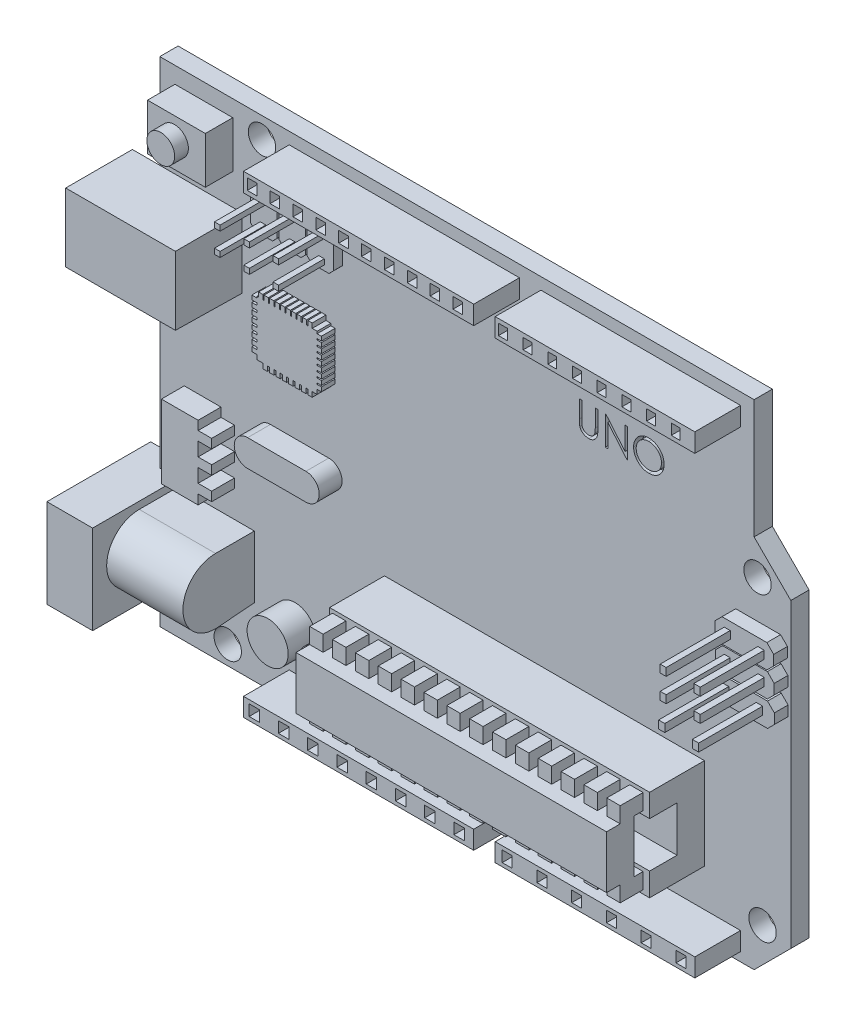
SolidWorks part; units mm, degrees
ref_plane "Front Plane" through (0, 0, 0) normal (0, 0, 1) x (1, 0, 0)
ref_plane "Top Plane" through (0, 0, 0) normal (0, 1, 0) x (1, 0, 0)
ref_plane "Right Plane" through (0, 0, 0) normal (1, 0, 0) x (0, 0, -1)
sketch "Sketch1" plane through (0, 0, 0) normal (0, 0, 1) x (1, 0, 0)
  line L0 (-30.3432, 34.8124) -> (32.6568, 34.8124)
  line L1 (-30.3432, 34.8124) -> (-30.3432, -19.1876)
  line L2 (-30.3432, -19.1876) -> (34.6568, -19.1876)
  line L3 (34.6568, -19.1876) -> (38.6728, -15.1716)
  line L4 (38.6728, -15.1716) -> (38.6728, 17.7963)
  line L5 (38.6728, 17.7963) -> (34.6568, 21.8124)
  line L6 (34.6568, 21.8124) -> (34.6568, 34.8124)
  line L7 (34.6568, 34.8124) -> (32.6568, 34.8124)
  dimension "D1" = 65
  dimension "D2" = 54
  dimension "D3" = 63
  dimension "D4" = 13
extrude "Boss-Extrude1" add sketch "Sketch1" along normal blind 2
sketch "Sketch2" plane through (0, 0, 2) normal (0, 0, 1) x (1, 0, 0)
  line L0 (-16.1908, 33.5246) -> (8.9881, 33.5246)
  line L1 (8.9881, 33.5246) -> (8.9881, 31.4811)
  line L2 (8.9881, 31.4811) -> (-16.1908, 31.4811)
  line L3 (-16.1908, 31.4811) -> (-16.1908, 33.5246)
  line L4 (11.3419, 33.5246) -> (33.1744, 33.5246)
  line L5 (33.1744, 33.5246) -> (33.1744, 31.4811)
  line L6 (33.1744, 31.4811) -> (11.3419, 31.4811)
  line L7 (11.3419, 31.4811) -> (11.3419, 33.5246)
extrude "Boss-Extrude2" add sketch "Sketch2" along normal blind 5
sketch "Sketch3" plane through (0, 0, 7) normal (0, 0, 1) x (1, 0, 0)
  line L0 (8.9881, 33.5246) -> (-16.1908, 33.5246) construction
  line L1 (-15.7782, 33.1261) -> (-14.7285, 33.1261)
  line L2 (-15.7782, 33.1261) -> (-15.7782, 31.9149)
  line L3 (-15.7782, 31.9149) -> (-14.7285, 31.9149)
  line L4 (-14.7285, 33.1261) -> (-14.7285, 31.9149)
  line L5 (-15.7782, 33.1261) -> (-14.7285, 31.9149) construction
  line L6 (-15.7782, 31.9149) -> (-14.7285, 33.1261) construction
  line L7 (-16.1908, 31.4811) -> (8.9881, 31.4811) construction
  line L8 (-13.2782, 33.1261) -> (-12.2285, 33.1261)
  line L9 (-12.2285, 33.1261) -> (-12.2285, 31.9149)
  line L10 (-13.2782, 31.9149) -> (-12.2285, 31.9149)
  line L11 (-13.2782, 33.1261) -> (-13.2782, 31.9149)
  line L12 (-10.7782, 33.1261) -> (-9.7285, 33.1261)
  line L13 (-9.7285, 33.1261) -> (-9.7285, 31.9149)
  line L14 (-10.7782, 31.9149) -> (-9.7285, 31.9149)
  line L15 (-10.7782, 33.1261) -> (-10.7782, 31.9149)
  line L16 (-8.2782, 33.1261) -> (-7.2285, 33.1261)
  line L17 (-7.2285, 33.1261) -> (-7.2285, 31.9149)
  line L18 (-8.2782, 31.9149) -> (-7.2285, 31.9149)
  line L19 (-8.2782, 33.1261) -> (-8.2782, 31.9149)
  line L20 (-5.7782, 33.1261) -> (-4.7285, 33.1261)
  line L21 (-4.7285, 33.1261) -> (-4.7285, 31.9149)
  line L22 (-5.7782, 31.9149) -> (-4.7285, 31.9149)
  line L23 (-5.7782, 33.1261) -> (-5.7782, 31.9149)
  line L24 (-3.2782, 33.1261) -> (-2.2285, 33.1261)
  line L25 (-2.2285, 33.1261) -> (-2.2285, 31.9149)
  line L26 (-3.2782, 31.9149) -> (-2.2285, 31.9149)
  line L27 (-3.2782, 33.1261) -> (-3.2782, 31.9149)
  line L28 (-0.7782, 33.1261) -> (0.2715, 33.1261)
  line L29 (0.2715, 33.1261) -> (0.2715, 31.9149)
  line L30 (-0.7782, 31.9149) -> (0.2715, 31.9149)
  line L31 (-0.7782, 33.1261) -> (-0.7782, 31.9149)
  line L32 (1.7218, 33.1261) -> (2.7715, 33.1261)
  line L33 (2.7715, 33.1261) -> (2.7715, 31.9149)
  line L34 (1.7218, 31.9149) -> (2.7715, 31.9149)
  line L35 (1.7218, 33.1261) -> (1.7218, 31.9149)
  line L36 (4.2218, 33.1261) -> (5.2715, 33.1261)
  line L37 (5.2715, 33.1261) -> (5.2715, 31.9149)
  line L38 (4.2218, 31.9149) -> (5.2715, 31.9149)
  line L39 (4.2218, 33.1261) -> (4.2218, 31.9149)
  line L40 (6.7218, 33.1261) -> (7.7715, 33.1261)
  line L41 (7.7715, 33.1261) -> (7.7715, 31.9149)
  line L42 (6.7218, 31.9149) -> (7.7715, 31.9149)
  line L43 (6.7218, 33.1261) -> (6.7218, 31.9149)
  point P0 (-15.2533, 32.5205)
  dimension "D1" = 0.3985
  dimension "D2" = 0.4337
  dimension "D3" = 10
extrude "Cut-Extrude1" cut sketch "Sketch3" against normal blind 5
sketch "Sketch4" plane through (0, 0, 7) normal (0, 0, 1) x (1, 0, 0)
  line L0 (33.1744, 33.5246) -> (11.3419, 33.5246) construction
  line L1 (11.6967, 33.0774) -> (12.6722, 33.0774)
  line L2 (11.6967, 33.0774) -> (11.6967, 31.8986)
  line L3 (11.6967, 31.8986) -> (12.6722, 31.8986)
  line L4 (12.6722, 33.0774) -> (12.6722, 31.8986)
  line L5 (11.6967, 33.0774) -> (12.6722, 31.8986) construction
  line L6 (11.6967, 31.8986) -> (12.6722, 33.0774) construction
  line L7 (11.3419, 31.4811) -> (33.1744, 31.4811) construction
  line L8 (14.3967, 33.0774) -> (15.3722, 33.0774)
  line L9 (15.3722, 33.0774) -> (15.3722, 31.8986)
  line L10 (14.3967, 31.8986) -> (15.3722, 31.8986)
  line L11 (14.3967, 33.0774) -> (14.3967, 31.8986)
  line L12 (17.0967, 33.0774) -> (18.0722, 33.0774)
  line L13 (18.0722, 33.0774) -> (18.0722, 31.8986)
  line L14 (17.0967, 31.8986) -> (18.0722, 31.8986)
  line L15 (17.0967, 33.0774) -> (17.0967, 31.8986)
  line L16 (19.7967, 33.0774) -> (20.7722, 33.0774)
  line L17 (20.7722, 33.0774) -> (20.7722, 31.8986)
  line L18 (19.7967, 31.8986) -> (20.7722, 31.8986)
  line L19 (19.7967, 33.0774) -> (19.7967, 31.8986)
  line L20 (22.4967, 33.0774) -> (23.4722, 33.0774)
  line L21 (23.4722, 33.0774) -> (23.4722, 31.8986)
  line L22 (22.4967, 31.8986) -> (23.4722, 31.8986)
  line L23 (22.4967, 33.0774) -> (22.4967, 31.8986)
  line L24 (25.1967, 33.0774) -> (26.1722, 33.0774)
  line L25 (26.1722, 33.0774) -> (26.1722, 31.8986)
  line L26 (25.1967, 31.8986) -> (26.1722, 31.8986)
  line L27 (25.1967, 33.0774) -> (25.1967, 31.8986)
  line L28 (27.8967, 33.0774) -> (28.8722, 33.0774)
  line L29 (28.8722, 33.0774) -> (28.8722, 31.8986)
  line L30 (27.8967, 31.8986) -> (28.8722, 31.8986)
  line L31 (27.8967, 33.0774) -> (27.8967, 31.8986)
  line L32 (30.5967, 33.0774) -> (31.5722, 33.0774)
  line L33 (31.5722, 33.0774) -> (31.5722, 31.8986)
  line L34 (30.5967, 31.8986) -> (31.5722, 31.8986)
  line L35 (30.5967, 33.0774) -> (30.5967, 31.8986)
  point P0 (12.1845, 32.488)
  dimension "D1" = 0.4472
  dimension "D2" = 0.4175
  dimension "D3" = 8
extrude "Cut-Extrude2" cut sketch "Sketch4" against normal blind 5
sketch "Sketch5" plane through (0, 0, 2) normal (0, 0, 1) x (1, 0, 0)
  line L0 (-16.1908, -16.2122) -> (8.9881, -16.2122)
  line L1 (8.9881, -16.2122) -> (8.9881, -18.2122)
  line L2 (8.9881, -18.2122) -> (-16.1908, -18.2122)
  line L3 (-16.1908, -18.2122) -> (-16.1908, -16.2122)
  line L4 (-16.1908, 33.5246) -> (-16.1908, 31.4811) construction
  line L5 (8.9881, 31.4811) -> (8.9881, 33.5246) construction
  line L8 (11.3419, -16.2122) -> (33.1744, -16.2122)
  line L9 (33.1744, -16.2122) -> (33.1744, -18.2122)
  line L10 (33.1744, -18.2122) -> (11.3419, -18.2122)
  line L11 (11.3419, -16.2122) -> (11.3419, -18.2122)
  line L12 (11.3419, 33.5246) -> (11.3419, 31.4811) construction
  line L13 (33.1744, 31.4811) -> (33.1744, 33.5246) construction
extrude "Boss-Extrude3" add sketch "Sketch5" along normal blind 5
sketch "Sketch6" plane through (0, 0, 7) normal (0, 0, 1) x (1, 0, 0)
  line L0 (8.9881, -16.2122) -> (-16.1908, -16.2122) construction
  line L1 (-15.572, -16.6122) -> (-14.4338, -16.6122)
  line L2 (-15.572, -16.6122) -> (-15.572, -17.8122)
  line L3 (-15.572, -17.8122) -> (-14.4338, -17.8122)
  line L4 (-14.4338, -16.6122) -> (-14.4338, -17.8122)
  line L5 (-15.572, -16.6122) -> (-14.4338, -17.8122) construction
  line L6 (-15.572, -17.8122) -> (-14.4338, -16.6122) construction
  line L7 (-16.1908, -18.2122) -> (8.9881, -18.2122) construction
  line L8 (-12.372, -16.6122) -> (-11.2338, -16.6122)
  line L9 (-11.2338, -16.6122) -> (-11.2338, -17.8122)
  line L10 (-12.372, -17.8122) -> (-11.2338, -17.8122)
  line L11 (-12.372, -16.6122) -> (-12.372, -17.8122)
  line L12 (-9.172, -16.6122) -> (-8.0338, -16.6122)
  line L13 (-8.0338, -16.6122) -> (-8.0338, -17.8122)
  line L14 (-9.172, -17.8122) -> (-8.0338, -17.8122)
  line L15 (-9.172, -16.6122) -> (-9.172, -17.8122)
  line L16 (-5.972, -16.6122) -> (-4.8338, -16.6122)
  line L17 (-4.8338, -16.6122) -> (-4.8338, -17.8122)
  line L18 (-5.972, -17.8122) -> (-4.8338, -17.8122)
  line L19 (-5.972, -16.6122) -> (-5.972, -17.8122)
  line L20 (-2.772, -16.6122) -> (-1.6338, -16.6122)
  line L21 (-1.6338, -16.6122) -> (-1.6338, -17.8122)
  line L22 (-2.772, -17.8122) -> (-1.6338, -17.8122)
  line L23 (-2.772, -16.6122) -> (-2.772, -17.8122)
  line L24 (0.428, -16.6122) -> (1.5662, -16.6122)
  line L25 (1.5662, -16.6122) -> (1.5662, -17.8122)
  line L26 (0.428, -17.8122) -> (1.5662, -17.8122)
  line L27 (0.428, -16.6122) -> (0.428, -17.8122)
  line L28 (3.628, -16.6122) -> (4.7662, -16.6122)
  line L29 (4.7662, -16.6122) -> (4.7662, -17.8122)
  line L30 (3.628, -17.8122) -> (4.7662, -17.8122)
  line L31 (3.628, -16.6122) -> (3.628, -17.8122)
  line L32 (6.828, -16.6122) -> (7.9662, -16.6122)
  line L33 (7.9662, -16.6122) -> (7.9662, -17.8122)
  line L34 (6.828, -17.8122) -> (7.9662, -17.8122)
  line L35 (6.828, -16.6122) -> (6.828, -17.8122)
  point P0 (-15.0029, -17.2122)
  dimension "D1" = 0.4
  dimension "D2" = 0.4
  dimension "D3" = 8
extrude "Cut-Extrude3" cut sketch "Sketch6" against normal blind 5
sketch "Sketch7" plane through (0, 0, 7) normal (0, 0, 1) x (1, 0, 0)
  line L0 (33.1744, -16.2122) -> (11.3419, -16.2122) construction
  line L1 (12.1099, -16.6122) -> (13.1873, -16.6122)
  line L2 (12.1099, -16.6122) -> (12.1099, -17.8122)
  line L3 (12.1099, -17.8122) -> (13.1873, -17.8122)
  line L4 (13.1873, -16.6122) -> (13.1873, -17.8122)
  line L5 (12.1099, -16.6122) -> (13.1873, -17.8122) construction
  line L6 (12.1099, -17.8122) -> (13.1873, -16.6122) construction
  line L7 (11.3419, -18.2122) -> (33.1744, -18.2122) construction
  line L8 (15.9099, -16.6122) -> (16.9873, -16.6122)
  line L9 (16.9873, -16.6122) -> (16.9873, -17.8122)
  line L10 (15.9099, -17.8122) -> (16.9873, -17.8122)
  line L11 (15.9099, -16.6122) -> (15.9099, -17.8122)
  line L12 (19.7099, -16.6122) -> (20.7873, -16.6122)
  line L13 (20.7873, -16.6122) -> (20.7873, -17.8122)
  line L14 (19.7099, -17.8122) -> (20.7873, -17.8122)
  line L15 (19.7099, -16.6122) -> (19.7099, -17.8122)
  line L16 (23.5099, -16.6122) -> (24.5873, -16.6122)
  line L17 (24.5873, -16.6122) -> (24.5873, -17.8122)
  line L18 (23.5099, -17.8122) -> (24.5873, -17.8122)
  line L19 (23.5099, -16.6122) -> (23.5099, -17.8122)
  line L20 (27.3099, -16.6122) -> (28.3873, -16.6122)
  line L21 (28.3873, -16.6122) -> (28.3873, -17.8122)
  line L22 (27.3099, -17.8122) -> (28.3873, -17.8122)
  line L23 (27.3099, -16.6122) -> (27.3099, -17.8122)
  line L24 (31.1099, -16.6122) -> (32.1873, -16.6122)
  line L25 (32.1873, -16.6122) -> (32.1873, -17.8122)
  line L26 (31.1099, -17.8122) -> (32.1873, -17.8122)
  line L27 (31.1099, -16.6122) -> (31.1099, -17.8122)
  point P0 (12.6486, -17.2122)
  dimension "D1" = 0.4
  dimension "D2" = 0.4
  dimension "D3" = 6
extrude "Cut-Extrude4" cut sketch "Sketch7" against normal blind 5
sketch "Sketch8" plane through (0, 0, 2) normal (0, 0, 1) x (1, 0, 0)
  circle A0 centre (35.0332, 18.1728) radius 1.5
  circle A1 centre (35.582, -14.5072) radius 1.5
  circle A2 centre (-22.9132, -17.1286) radius 1.5
  circle A3 centre (-19.1683, 32.5286) radius 1.5
  dimension "D1" = 3
  dimension "D2" = 3
  dimension "D3" = 3
  dimension "D4" = 3
extrude "Cut-Extrude5" cut sketch "Sketch8" against normal blind 5
sketch "Sketch9" plane through (0, 0, 2) normal (0, 0, 1) x (1, 0, 0)
  line L1 (-5.7706, -2.0923) -> (29.2294, -2.0923)
  line L2 (-5.7706, -2.0923) -> (-5.7706, -12.0923)
  line L3 (-5.7706, -12.0923) -> (29.2294, -12.0923)
  line L4 (29.2294, -2.0923) -> (29.2294, -12.0923)
  line L5 (-5.7706, -2.0923) -> (29.2294, -12.0923) construction
  line L6 (-5.7706, -12.0923) -> (29.2294, -2.0923) construction
  point P0 (11.7294, -7.0923)
  dimension "D1" = 35
  dimension "D2" = 10
extrude "Boss-Extrude4" add sketch "Sketch9" along normal blind 6
sketch "Sketch10" plane through (29.2294, 0, 0) normal (1, 0, 0) x (0, 0, -1)
  line L0 (-8, -4.5923) -> (-5.0036, -4.5923)
  line L1 (-8, -12.0923) -> (-8, -2.0923) construction
  line L2 (-5.0036, -4.5923) -> (-5.0036, -9.5561)
  line L3 (-5.0036, -9.5561) -> (-8, -9.5561)
  line L4 (-8, -2.0923) -> (-2, -2.0923) construction
  line L5 (-8, -12.0923) -> (-2, -12.0923) construction
  line L6 (-8, -4.5923) -> (-8, -9.5561)
  dimension "D1" = 2.5
  dimension "D2" = 2.5362
extrude "Cut-Extrude7" cut sketch "Sketch10" against normal blind 35
sketch "Sketch11" plane through (0, 0, 8) normal (0, 0, 1) x (1, 0, 0)
  line L0 (29.2294, -2.0923) -> (-5.7706, -2.0923) construction
  line L1 (-5.4532, -2.4705) -> (-3.984, -2.4705)
  line L2 (-5.4532, -2.4705) -> (-5.4532, -4.1923)
  line L3 (-5.4532, -4.1923) -> (-3.984, -4.1923)
  line L4 (-3.984, -2.4705) -> (-3.984, -4.1923)
  line L5 (-5.4532, -2.4705) -> (-3.984, -4.1923) construction
  line L6 (-5.4532, -4.1923) -> (-3.984, -2.4705) construction
  line L7 (-5.7706, -4.5923) -> (29.2294, -4.5923) construction
  line L8 (-5.4532, -9.9563) -> (-3.984, -11.6781) construction
  line L9 (-5.4532, -9.9563) -> (-5.4532, -11.6781)
  line L10 (-5.4532, -11.6781) -> (-3.984, -11.6781)
  line L11 (-3.984, -9.9563) -> (-3.984, -11.6781)
  line L12 (-5.4532, -11.6781) -> (-3.984, -9.9563) construction
  line L13 (-5.4532, -9.9563) -> (-3.984, -9.9563)
  line L14 (-2.9532, -2.4705) -> (-1.484, -2.4705)
  line L15 (-1.484, -2.4705) -> (-1.484, -4.1923)
  line L16 (-2.9532, -4.1923) -> (-1.484, -4.1923)
  line L17 (-2.9532, -2.4705) -> (-2.9532, -4.1923)
  line L18 (-2.9532, -9.9563) -> (-1.484, -9.9563)
  line L19 (-1.484, -9.9563) -> (-1.484, -11.6781)
  line L20 (-2.9532, -11.6781) -> (-1.484, -11.6781)
  line L21 (-2.9532, -9.9563) -> (-2.9532, -11.6781)
  line L22 (-0.4532, -2.4705) -> (1.016, -2.4705)
  line L23 (1.016, -2.4705) -> (1.016, -4.1923)
  line L24 (-0.4532, -4.1923) -> (1.016, -4.1923)
  line L25 (-0.4532, -2.4705) -> (-0.4532, -4.1923)
  line L26 (-0.4532, -9.9563) -> (1.016, -9.9563)
  line L27 (1.016, -9.9563) -> (1.016, -11.6781)
  line L28 (-0.4532, -11.6781) -> (1.016, -11.6781)
  line L29 (-0.4532, -9.9563) -> (-0.4532, -11.6781)
  line L30 (2.0468, -2.4705) -> (3.516, -2.4705)
  line L31 (3.516, -2.4705) -> (3.516, -4.1923)
  line L32 (2.0468, -4.1923) -> (3.516, -4.1923)
  line L33 (2.0468, -2.4705) -> (2.0468, -4.1923)
  line L34 (2.0468, -9.9563) -> (3.516, -9.9563)
  line L35 (3.516, -9.9563) -> (3.516, -11.6781)
  line L36 (2.0468, -11.6781) -> (3.516, -11.6781)
  line L37 (2.0468, -9.9563) -> (2.0468, -11.6781)
  line L38 (4.5468, -2.4705) -> (6.016, -2.4705)
  line L39 (6.016, -2.4705) -> (6.016, -4.1923)
  line L40 (4.5468, -4.1923) -> (6.016, -4.1923)
  line L41 (4.5468, -2.4705) -> (4.5468, -4.1923)
  line L42 (4.5468, -9.9563) -> (6.016, -9.9563)
  line L43 (6.016, -9.9563) -> (6.016, -11.6781)
  line L44 (4.5468, -11.6781) -> (6.016, -11.6781)
  line L45 (4.5468, -9.9563) -> (4.5468, -11.6781)
  line L46 (7.0468, -2.4705) -> (8.516, -2.4705)
  line L47 (8.516, -2.4705) -> (8.516, -4.1923)
  line L48 (7.0468, -4.1923) -> (8.516, -4.1923)
  line L49 (7.0468, -2.4705) -> (7.0468, -4.1923)
  line L50 (7.0468, -9.9563) -> (8.516, -9.9563)
  line L51 (8.516, -9.9563) -> (8.516, -11.6781)
  line L52 (7.0468, -11.6781) -> (8.516, -11.6781)
  line L53 (7.0468, -9.9563) -> (7.0468, -11.6781)
  line L54 (9.5468, -2.4705) -> (11.016, -2.4705)
  line L55 (11.016, -2.4705) -> (11.016, -4.1923)
  line L56 (9.5468, -4.1923) -> (11.016, -4.1923)
  line L57 (9.5468, -2.4705) -> (9.5468, -4.1923)
  line L58 (9.5468, -9.9563) -> (11.016, -9.9563)
  line L59 (11.016, -9.9563) -> (11.016, -11.6781)
  line L60 (9.5468, -11.6781) -> (11.016, -11.6781)
  line L61 (9.5468, -9.9563) -> (9.5468, -11.6781)
  line L62 (12.0468, -2.4705) -> (13.516, -2.4705)
  line L63 (13.516, -2.4705) -> (13.516, -4.1923)
  line L64 (12.0468, -4.1923) -> (13.516, -4.1923)
  line L65 (12.0468, -2.4705) -> (12.0468, -4.1923)
  line L66 (12.0468, -9.9563) -> (13.516, -9.9563)
  line L67 (13.516, -9.9563) -> (13.516, -11.6781)
  line L68 (12.0468, -11.6781) -> (13.516, -11.6781)
  line L69 (12.0468, -9.9563) -> (12.0468, -11.6781)
  line L70 (14.5468, -2.4705) -> (16.016, -2.4705)
  line L71 (16.016, -2.4705) -> (16.016, -4.1923)
  line L72 (14.5468, -4.1923) -> (16.016, -4.1923)
  line L73 (14.5468, -2.4705) -> (14.5468, -4.1923)
  line L74 (14.5468, -9.9563) -> (16.016, -9.9563)
  line L75 (16.016, -9.9563) -> (16.016, -11.6781)
  line L76 (14.5468, -11.6781) -> (16.016, -11.6781)
  line L77 (14.5468, -9.9563) -> (14.5468, -11.6781)
  line L78 (17.0468, -2.4705) -> (18.516, -2.4705)
  line L79 (18.516, -2.4705) -> (18.516, -4.1923)
  line L80 (17.0468, -4.1923) -> (18.516, -4.1923)
  line L81 (17.0468, -2.4705) -> (17.0468, -4.1923)
  line L82 (17.0468, -9.9563) -> (18.516, -9.9563)
  line L83 (18.516, -9.9563) -> (18.516, -11.6781)
  line L84 (17.0468, -11.6781) -> (18.516, -11.6781)
  line L85 (17.0468, -9.9563) -> (17.0468, -11.6781)
  line L86 (19.5468, -2.4705) -> (21.016, -2.4705)
  line L87 (21.016, -2.4705) -> (21.016, -4.1923)
  line L88 (19.5468, -4.1923) -> (21.016, -4.1923)
  line L89 (19.5468, -2.4705) -> (19.5468, -4.1923)
  line L90 (19.5468, -9.9563) -> (21.016, -9.9563)
  line L91 (21.016, -9.9563) -> (21.016, -11.6781)
  line L92 (19.5468, -11.6781) -> (21.016, -11.6781)
  line L93 (19.5468, -9.9563) -> (19.5468, -11.6781)
  line L94 (22.0468, -2.4705) -> (23.516, -2.4705)
  line L95 (23.516, -2.4705) -> (23.516, -4.1923)
  line L96 (22.0468, -4.1923) -> (23.516, -4.1923)
  line L97 (22.0468, -2.4705) -> (22.0468, -4.1923)
  line L98 (22.0468, -9.9563) -> (23.516, -9.9563)
  line L99 (23.516, -9.9563) -> (23.516, -11.6781)
  line L100 (22.0468, -11.6781) -> (23.516, -11.6781)
  line L101 (22.0468, -9.9563) -> (22.0468, -11.6781)
  line L102 (24.5468, -2.4705) -> (26.016, -2.4705)
  line L103 (26.016, -2.4705) -> (26.016, -4.1923)
  line L104 (24.5468, -4.1923) -> (26.016, -4.1923)
  line L105 (24.5468, -2.4705) -> (24.5468, -4.1923)
  line L106 (24.5468, -9.9563) -> (26.016, -9.9563)
  line L107 (26.016, -9.9563) -> (26.016, -11.6781)
  line L108 (24.5468, -11.6781) -> (26.016, -11.6781)
  line L109 (24.5468, -9.9563) -> (24.5468, -11.6781)
  line L110 (27.0468, -2.4705) -> (28.516, -2.4705)
  line L111 (28.516, -2.4705) -> (28.516, -4.1923)
  line L112 (27.0468, -4.1923) -> (28.516, -4.1923)
  line L113 (27.0468, -2.4705) -> (27.0468, -4.1923)
  line L114 (27.0468, -9.9563) -> (28.516, -9.9563)
  line L115 (28.516, -9.9563) -> (28.516, -11.6781)
  line L116 (27.0468, -11.6781) -> (28.516, -11.6781)
  line L117 (27.0468, -9.9563) -> (27.0468, -11.6781)
  point P0 (-4.7186, -3.3314)
  point P9 (-4.7186, -10.8172)
  dimension "D1" = 0.3782
  dimension "D2" = 0.4
  dimension "D3" = 14
extrude "Cut-Extrude8" cut sketch "Sketch11" against normal blind 5
sketch "Sketch12" plane through (0, 0, 8) normal (0, 0, 1) x (1, 0, 0)
  line L0 (-5.4532, -2.4705) -> (-3.984, -2.4705)
  line L1 (-3.984, -2.4705) -> (-3.984, -4.1923)
  line L2 (-3.984, -4.1923) -> (-5.4532, -4.1923)
  line L3 (-5.4532, -4.1923) -> (-5.4532, -2.4705)
  line L4 (-5.4532, -9.9563) -> (-5.4532, -11.6781)
  line L5 (-5.4532, -11.6781) -> (-3.984, -11.6781)
  line L6 (-3.984, -11.6781) -> (-3.984, -9.9563)
  line L7 (-3.984, -9.9563) -> (-5.4532, -9.9563)
  line L8 (-2.9532, -2.4705) -> (-1.484, -2.4705)
  line L9 (-1.484, -2.4705) -> (-1.484, -4.1923)
  line L10 (-1.484, -4.1923) -> (-2.9532, -4.1923)
  line L11 (-2.9532, -4.1923) -> (-2.9532, -2.4705)
  line L12 (-1.484, -9.9563) -> (-2.9532, -9.9563)
  line L13 (-1.484, -11.6781) -> (-1.484, -9.9563)
  line L14 (-2.9532, -11.6781) -> (-1.484, -11.6781)
  line L15 (-2.9532, -9.9563) -> (-2.9532, -11.6781)
  line L16 (-0.4532, -2.4705) -> (1.016, -2.4705)
  line L17 (1.016, -2.4705) -> (1.016, -4.1923)
  line L18 (1.016, -4.1923) -> (-0.4532, -4.1923)
  line L19 (-0.4532, -4.1923) -> (-0.4532, -2.4705)
  line L20 (1.016, -9.9563) -> (-0.4532, -9.9563)
  line L21 (1.016, -11.6781) -> (1.016, -9.9563)
  line L22 (-0.4532, -11.6781) -> (1.016, -11.6781)
  line L23 (-0.4532, -9.9563) -> (-0.4532, -11.6781)
  line L24 (2.0468, -2.4705) -> (3.516, -2.4705)
  line L25 (3.516, -2.4705) -> (3.516, -4.1923)
  line L26 (3.516, -4.1923) -> (2.0468, -4.1923)
  line L27 (2.0468, -4.1923) -> (2.0468, -2.4705)
  line L28 (3.516, -9.9563) -> (2.0468, -9.9563)
  line L29 (3.516, -11.6781) -> (3.516, -9.9563)
  line L30 (2.0468, -11.6781) -> (3.516, -11.6781)
  line L31 (2.0468, -9.9563) -> (2.0468, -11.6781)
  line L32 (4.5468, -2.4705) -> (6.016, -2.4705)
  line L33 (6.016, -2.4705) -> (6.016, -4.1923)
  line L34 (6.016, -4.1923) -> (4.5468, -4.1923)
  line L35 (4.5468, -4.1923) -> (4.5468, -2.4705)
  line L36 (6.016, -9.9563) -> (4.5468, -9.9563)
  line L37 (6.016, -11.6781) -> (6.016, -9.9563)
  line L38 (4.5468, -11.6781) -> (6.016, -11.6781)
  line L39 (4.5468, -9.9563) -> (4.5468, -11.6781)
  line L40 (7.0468, -2.4705) -> (8.516, -2.4705)
  line L41 (8.516, -2.4705) -> (8.516, -4.1923)
  line L42 (8.516, -4.1923) -> (7.0468, -4.1923)
  line L43 (7.0468, -4.1923) -> (7.0468, -2.4705)
  line L44 (8.516, -9.9563) -> (7.0468, -9.9563)
  line L45 (8.516, -11.6781) -> (8.516, -9.9563)
  line L46 (7.0468, -11.6781) -> (8.516, -11.6781)
  line L47 (7.0468, -9.9563) -> (7.0468, -11.6781)
  line L48 (9.5468, -2.4705) -> (11.016, -2.4705)
  line L49 (11.016, -2.4705) -> (11.016, -4.1923)
  line L50 (11.016, -4.1923) -> (9.5468, -4.1923)
  line L51 (9.5468, -4.1923) -> (9.5468, -2.4705)
  line L52 (11.016, -9.9563) -> (9.5468, -9.9563)
  line L53 (11.016, -11.6781) -> (11.016, -9.9563)
  line L54 (9.5468, -11.6781) -> (11.016, -11.6781)
  line L55 (9.5468, -9.9563) -> (9.5468, -11.6781)
  line L56 (12.0468, -2.4705) -> (13.516, -2.4705)
  line L57 (13.516, -2.4705) -> (13.516, -4.1923)
  line L58 (13.516, -4.1923) -> (12.0468, -4.1923)
  line L59 (12.0468, -4.1923) -> (12.0468, -2.4705)
  line L60 (13.516, -9.9563) -> (12.0468, -9.9563)
  line L61 (13.516, -11.6781) -> (13.516, -9.9563)
  line L62 (12.0468, -11.6781) -> (13.516, -11.6781)
  line L63 (12.0468, -9.9563) -> (12.0468, -11.6781)
  line L64 (14.5468, -2.4705) -> (16.016, -2.4705)
  line L65 (16.016, -2.4705) -> (16.016, -4.1923)
  line L66 (16.016, -4.1923) -> (14.5468, -4.1923)
  line L67 (14.5468, -4.1923) -> (14.5468, -2.4705)
  line L68 (16.016, -9.9563) -> (14.5468, -9.9563)
  line L69 (16.016, -11.6781) -> (16.016, -9.9563)
  line L70 (14.5468, -11.6781) -> (16.016, -11.6781)
  line L71 (14.5468, -9.9563) -> (14.5468, -11.6781)
  line L72 (17.0468, -2.4705) -> (18.516, -2.4705)
  line L73 (18.516, -2.4705) -> (18.516, -4.1923)
  line L74 (18.516, -4.1923) -> (17.0468, -4.1923)
  line L75 (17.0468, -4.1923) -> (17.0468, -2.4705)
  line L76 (18.516, -9.9563) -> (17.0468, -9.9563)
  line L77 (18.516, -11.6781) -> (18.516, -9.9563)
  line L78 (17.0468, -11.6781) -> (18.516, -11.6781)
  line L79 (17.0468, -9.9563) -> (17.0468, -11.6781)
  line L80 (19.5468, -2.4705) -> (21.016, -2.4705)
  line L81 (21.016, -2.4705) -> (21.016, -4.1923)
  line L82 (21.016, -4.1923) -> (19.5468, -4.1923)
  line L83 (19.5468, -4.1923) -> (19.5468, -2.4705)
  line L84 (21.016, -9.9563) -> (19.5468, -9.9563)
  line L85 (21.016, -11.6781) -> (21.016, -9.9563)
  line L86 (19.5468, -11.6781) -> (21.016, -11.6781)
  line L87 (19.5468, -9.9563) -> (19.5468, -11.6781)
  line L88 (22.0468, -2.4705) -> (23.516, -2.4705)
  line L89 (23.516, -2.4705) -> (23.516, -4.1923)
  line L90 (23.516, -4.1923) -> (22.0468, -4.1923)
  line L91 (22.0468, -4.1923) -> (22.0468, -2.4705)
  line L92 (23.516, -9.9563) -> (22.0468, -9.9563)
  line L93 (23.516, -11.6781) -> (23.516, -9.9563)
  line L94 (22.0468, -11.6781) -> (23.516, -11.6781)
  line L95 (22.0468, -9.9563) -> (22.0468, -11.6781)
  line L96 (24.5468, -2.4705) -> (26.016, -2.4705)
  line L97 (26.016, -2.4705) -> (26.016, -4.1923)
  line L98 (26.016, -4.1923) -> (24.5468, -4.1923)
  line L99 (24.5468, -4.1923) -> (24.5468, -2.4705)
  line L100 (26.016, -9.9563) -> (24.5468, -9.9563)
  line L101 (26.016, -11.6781) -> (26.016, -9.9563)
  line L102 (24.5468, -11.6781) -> (26.016, -11.6781)
  line L103 (24.5468, -9.9563) -> (24.5468, -11.6781)
  line L104 (27.0468, -2.4705) -> (28.516, -2.4705)
  line L105 (28.516, -2.4705) -> (28.516, -4.1923)
  line L106 (28.516, -4.1923) -> (27.0468, -4.1923)
  line L107 (27.0468, -4.1923) -> (27.0468, -2.4705)
  line L108 (28.516, -9.9563) -> (27.0468, -9.9563)
  line L109 (28.516, -11.6781) -> (28.516, -9.9563)
  line L110 (27.0468, -11.6781) -> (28.516, -11.6781)
  line L111 (27.0468, -9.9563) -> (27.0468, -11.6781)
  dimension "D1" = 14
extrude "Boss-Extrude5" add sketch "Sketch12" along normal blind 2.5 and the other way blind 4
sketch "Sketch14" plane through (0, 0, 10.5) normal (0, 0, 1) x (1, 0, 0)
  line L0 (-5.4532, -4.1923) -> (-5.4532, -9.9563)
  line L1 (-5.4532, -9.9563) -> (28.516, -9.9563)
  line L2 (28.516, -9.9563) -> (28.516, -4.1923)
  line L3 (28.516, -4.1923) -> (-5.4532, -4.1923)
extrude "Boss-Extrude6" add sketch "Sketch14" along normal blind 1.5 and the other way blind 1.5
sketch "Sketch15" plane through (0, 0, 2) normal (0, 0, 1) x (1, 0, 0)
  line L0 (32.6488, 14.0019) -> (37.5544, 14.0019)
  line L1 (37.5544, 14.0019) -> (38.3009, 13.2554)
  line L2 (38.3009, 13.2554) -> (38.3009, 12.1534)
  line L3 (38.3009, 12.1534) -> (37.5544, 11.4069)
  line L4 (37.5544, 11.4069) -> (32.6488, 11.4069)
  line L5 (32.6488, 11.4069) -> (31.9023, 12.1534)
  line L6 (31.9023, 12.1534) -> (31.9023, 13.2554)
  line L7 (31.9023, 13.2554) -> (32.6488, 14.0019)
  line L8 (31.9575, 9.4322) -> (31.9575, 10.5342)
  line L9 (38.356, 9.4322) -> (37.6095, 8.6857)
  line L10 (37.6095, 8.6857) -> (32.704, 8.6857)
  line L11 (32.704, 11.2807) -> (37.6095, 11.2807)
  line L12 (31.9575, 10.5342) -> (32.704, 11.2807)
  line L13 (38.356, 10.5342) -> (38.356, 9.4322)
  line L14 (32.704, 8.6857) -> (31.9575, 9.4322)
  line L15 (37.6095, 11.2807) -> (38.356, 10.5342)
  line L16 (37.628, 8.4949) -> (38.3745, 7.7484)
  line L17 (32.7224, 5.9) -> (31.9759, 6.6465)
  line L18 (32.7224, 8.4949) -> (37.628, 8.4949)
  line L19 (38.3745, 7.7484) -> (38.3745, 6.6465)
  line L20 (37.628, 5.9) -> (32.7224, 5.9)
  line L21 (31.9759, 6.6465) -> (31.9759, 7.7484)
  line L22 (38.3745, 6.6465) -> (37.628, 5.9)
  line L23 (31.9759, 7.7484) -> (32.7224, 8.4949)
extrude "Boss-Extrude7" add sketch "Sketch15" along normal blind 1.5
sketch "Sketch16" plane through (0, 0, 3.5) normal (0, 0, 1) x (1, 0, 0)
  line L0 (37.2554, 10.5645) -> (37.2554, 9.7045)
  line L1 (32.8824, 13.1319) -> (33.5564, 13.1319)
  line L2 (32.8824, 13.1319) -> (32.8824, 12.2719)
  line L3 (32.8824, 12.2719) -> (33.5564, 12.2719)
  line L4 (33.5564, 13.1319) -> (33.5564, 12.2719)
  line L5 (32.8824, 13.1319) -> (33.5564, 12.2719) construction
  line L6 (32.8824, 12.2719) -> (33.5564, 13.1319) construction
  line L7 (36.5663, 13.1319) -> (37.2635, 13.1319)
  line L8 (36.5663, 13.1319) -> (36.5663, 12.2719)
  line L9 (36.5663, 12.2719) -> (37.2635, 12.2719)
  line L10 (37.2635, 13.1319) -> (37.2635, 12.2719)
  line L11 (36.5663, 13.1319) -> (37.2635, 12.2719) construction
  line L12 (36.5663, 12.2719) -> (37.2635, 13.1319) construction
  line L13 (36.5581, 9.7045) -> (37.2554, 10.5645) construction
  line L14 (32.8742, 9.7045) -> (33.5483, 9.7045)
  line L15 (32.8742, 10.5645) -> (32.8742, 9.7045)
  line L16 (32.8742, 10.5645) -> (33.5483, 9.7045) construction
  line L17 (36.5581, 10.5645) -> (37.2554, 9.7045) construction
  line L18 (36.5581, 9.7045) -> (37.2554, 9.7045)
  line L19 (32.8742, 9.7045) -> (33.5483, 10.5645) construction
  line L20 (36.5581, 10.5645) -> (37.2554, 10.5645)
  line L21 (36.5581, 10.5645) -> (36.5581, 9.7045)
  line L22 (32.8742, 10.5645) -> (33.5483, 10.5645)
  line L23 (33.5483, 10.5645) -> (33.5483, 9.7045)
  line L24 (36.3976, 6.8925) -> (37.0949, 6.8925)
  line L25 (32.7137, 6.8925) -> (33.3877, 6.8925)
  line L26 (36.3976, 7.7525) -> (36.3976, 6.8925)
  line L27 (36.3976, 7.7525) -> (37.0949, 6.8925) construction
  line L28 (32.7137, 6.8925) -> (33.3877, 7.7525) construction
  line L29 (32.7137, 7.7525) -> (32.7137, 6.8925)
  line L30 (33.3877, 7.7525) -> (33.3877, 6.8925)
  line L31 (37.0949, 7.7525) -> (37.0949, 6.8925)
  line L32 (32.7137, 7.7525) -> (33.3877, 7.7525)
  line L33 (36.3976, 7.7525) -> (37.0949, 7.7525)
  line L34 (32.7137, 7.7525) -> (33.3877, 6.8925) construction
  line L35 (36.3976, 6.8925) -> (37.0949, 7.7525) construction
  point P0 (33.2194, 12.7019)
  point P5 (36.9149, 12.7019)
  point P10 (33.2112, 10.1345)
  point P15 (36.9068, 10.1345)
  point P20 (33.0507, 7.3225)
  point P25 (36.7462, 7.3225)
extrude "Cut-Extrude9" cut sketch "Sketch16" against normal blind 0.7
sketch "Sketch17" plane through (0, 0, 3.5) normal (0, 0, 1) x (1, 0, 0)
  line L0 (33.3877, 7.7525) -> (32.7137, 7.7525) construction
  line L1 (32.7137, 7.7525) -> (32.7137, 6.8925) construction
  line L2 (32.7137, 6.8925) -> (33.3877, 6.8925) construction
  line L3 (33.3877, 6.8925) -> (33.3877, 7.7525) construction
  line L4 (33.3877, 7.7525) -> (32.7137, 7.7525)
  line L5 (32.7137, 7.7525) -> (32.7137, 6.8925)
  line L6 (32.7137, 6.8925) -> (33.3877, 6.8925)
  line L7 (33.3877, 6.8925) -> (33.3877, 7.7525)
  line L8 (36.3976, 7.7525) -> (36.3976, 6.8925) construction
  line L9 (36.3976, 6.8925) -> (37.0949, 6.8925) construction
  line L10 (37.0949, 6.8925) -> (37.0949, 7.7525) construction
  line L11 (37.0949, 7.7525) -> (36.3976, 7.7525) construction
  line L12 (36.3976, 7.7525) -> (36.3976, 6.8925)
  line L13 (36.3976, 6.8925) -> (37.0949, 6.8925)
  line L14 (37.0949, 6.8925) -> (37.0949, 7.7525)
  line L15 (37.0949, 7.7525) -> (36.3976, 7.7525)
  line L16 (37.2679, 10.5509) -> (36.5707, 10.5509)
  line L17 (33.5363, 9.691) -> (33.5363, 10.5509)
  line L18 (33.5363, 10.5509) -> (32.8868, 10.5509)
  line L19 (36.5707, 10.5509) -> (36.5707, 9.691)
  line L20 (32.8868, 9.691) -> (33.5363, 9.691)
  line L21 (37.2679, 9.691) -> (37.2679, 10.5509)
  line L22 (32.8868, 10.5509) -> (32.8868, 9.691)
  line L23 (36.5707, 9.691) -> (37.2679, 9.691)
  line L24 (32.8868, 13.128) -> (32.8868, 12.2858)
  line L25 (36.5707, 12.2653) -> (37.2679, 12.2653)
  line L26 (37.2679, 12.2653) -> (37.2679, 13.1359)
  line L27 (36.5707, 13.1359) -> (36.5707, 12.2653)
  line L28 (33.5363, 12.2858) -> (33.5363, 13.128)
  line L29 (37.2679, 13.1359) -> (36.5707, 13.1359)
  line L30 (33.5363, 13.128) -> (32.8868, 13.128)
  line L31 (32.8868, 12.2858) -> (33.5363, 12.2858)
extrude "Boss-Extrude8" add sketch "Sketch17" along normal blind 7 and the other way blind 0.7
sketch "Sketch18" plane through (0, 0, 2) normal (0, 0, 1) x (1, 0, 0)
  line L0 (-18.8352, 28.6046) -> (-17.1117, 28.6046)
  line L1 (-17.1117, 28.6046) -> (-16.5171, 28.0164)
  line L2 (-16.5171, 28.0164) -> (-16.5171, 25.003)
  line L3 (-16.5171, 25.003) -> (-17.0044, 24.5104)
  line L4 (-17.0044, 24.5104) -> (-18.8938, 24.5104)
  line L5 (-18.8938, 24.5104) -> (-19.4171, 25.028)
  line L6 (-19.4171, 25.028) -> (-19.4171, 28.0164)
  line L7 (-19.4171, 28.0164) -> (-18.8352, 28.6046)
  line L8 (-15.7252, 28.5902) -> (-14.0016, 28.5902)
  line L9 (-16.307, 25.0137) -> (-16.307, 28.0021)
  line L10 (-13.407, 28.0021) -> (-13.407, 24.9887)
  line L11 (-13.407, 24.9887) -> (-13.8943, 24.4961)
  line L12 (-16.307, 28.0021) -> (-15.7252, 28.5902)
  line L13 (-13.8943, 24.4961) -> (-15.7838, 24.4961)
  line L14 (-14.0016, 28.5902) -> (-13.407, 28.0021)
  line L15 (-15.7838, 24.4961) -> (-16.307, 25.0137)
  line L16 (-12.6756, 28.6046) -> (-10.952, 28.6046)
  line L17 (-10.3574, 28.0164) -> (-10.3574, 25.003)
  line L18 (-13.2574, 25.028) -> (-13.2574, 28.0164)
  line L19 (-12.7342, 24.5104) -> (-13.2574, 25.028)
  line L20 (-13.2574, 28.0164) -> (-12.6756, 28.6046)
  line L21 (-10.952, 28.6046) -> (-10.3574, 28.0164)
  line L22 (-10.3574, 25.003) -> (-10.8447, 24.5104)
  line L23 (-10.8447, 24.5104) -> (-12.7342, 24.5104)
  dimension "D1" = 2.9
  dimension "D2" = 2.9
extrude "Boss-Extrude9" add sketch "Sketch18" along normal blind 1
sketch "Sketch19" plane through (0, 0, 3) normal (0, 0, 1) x (1, 0, 0)
  line L0 (-17.7495, 25.6524) -> (-17.7495, 25.0701)
  line L1 (-18.3624, 28.1499) -> (-17.7495, 28.1499)
  line L2 (-18.3624, 28.1499) -> (-18.3624, 27.5676)
  line L3 (-18.3624, 27.5676) -> (-17.7495, 27.5676)
  line L4 (-17.7495, 28.1499) -> (-17.7495, 27.5676)
  line L5 (-18.3624, 28.1499) -> (-17.7495, 27.5676) construction
  line L6 (-18.3624, 27.5676) -> (-17.7495, 28.1499) construction
  line L7 (-18.3624, 25.6524) -> (-17.7495, 25.0701) construction
  line L8 (-18.3624, 25.6524) -> (-17.7495, 25.6524)
  line L9 (-18.3624, 25.0701) -> (-17.7495, 25.6524) construction
  line L10 (-18.3624, 25.6524) -> (-18.3624, 25.0701)
  line L11 (-18.3624, 25.0701) -> (-17.7495, 25.0701)
  line L12 (-15.1624, 28.1499) -> (-14.5495, 28.1499)
  line L13 (-14.5495, 28.1499) -> (-14.5495, 27.5676)
  line L14 (-15.1624, 27.5676) -> (-14.5495, 27.5676)
  line L15 (-15.1624, 28.1499) -> (-15.1624, 27.5676)
  line L16 (-15.1624, 25.6524) -> (-14.5495, 25.6524)
  line L17 (-14.5495, 25.6524) -> (-14.5495, 25.0701)
  line L18 (-15.1624, 25.0701) -> (-14.5495, 25.0701)
  line L19 (-15.1624, 25.6524) -> (-15.1624, 25.0701)
  line L20 (-11.9624, 28.1499) -> (-11.3495, 28.1499)
  line L21 (-11.3495, 28.1499) -> (-11.3495, 27.5676)
  line L22 (-11.9624, 27.5676) -> (-11.3495, 27.5676)
  line L23 (-11.9624, 28.1499) -> (-11.9624, 27.5676)
  line L24 (-11.9624, 25.6524) -> (-11.3495, 25.6524)
  line L25 (-11.3495, 25.6524) -> (-11.3495, 25.0701)
  line L26 (-11.9624, 25.0701) -> (-11.3495, 25.0701)
  line L27 (-11.9624, 25.6524) -> (-11.9624, 25.0701)
  point P0 (-18.0559, 27.8588)
  point P5 (-18.0559, 25.3613)
  dimension "D1" = 3
extrude "Boss-Extrude10" add sketch "Sketch19" along normal blind 5
sketch "Sketch20" plane through (0, 0, 2) normal (0, 0, 1) x (1, 0, 0)
  line L0 (-18.2421, 4.5541) -> (-11.8661, 4.5541) construction
  line L1 (-18.2421, 6.0153) -> (-11.8661, 6.0153)
  line L2 (-18.2421, 3.093) -> (-11.8661, 3.093)
  arc A0 (-18.2421, 6.0153) -> (-18.2421, 3.093) centre (-18.2421, 4.5541) ccw
  arc A1 (-11.8661, 3.093) -> (-11.8661, 6.0153) centre (-11.8661, 4.5541) ccw
  point P2 (-15.0541, 4.5541)
extrude "Boss-Extrude11" add sketch "Sketch20" along normal blind 2.5
sketch "Sketch21" plane through (0, 0, 2) normal (0, 0, 1) x (1, 0, 0)
  line L1 (-18.2297, 18.8972) -> (-11.6387, 18.8972)
  line L2 (-18.2297, 18.8972) -> (-18.2297, 12.9054)
  line L3 (-18.2297, 12.9054) -> (-11.6387, 12.9054)
  line L4 (-11.6387, 18.8972) -> (-11.6387, 12.9054)
  line L5 (-18.2297, 18.8972) -> (-11.6387, 12.9054) construction
  line L6 (-18.2297, 12.9054) -> (-11.6387, 18.8972) construction
  point P0 (-14.9342, 15.9013)
extrude "Boss-Extrude12" add sketch "Sketch21" along normal blind 1.5
sketch "Sketch22" plane through (0, 0, 3.5) normal (0, 0, 1) x (1, 0, 0)
  line L0 (-18.0421, 18.8972) -> (-18.0421, 19.4143)
  line L1 (-11.6387, 18.8972) -> (-18.2297, 18.8972) construction
  line L2 (-18.0421, 19.4143) -> (-17.5747, 19.4143)
  line L3 (-17.5747, 19.4143) -> (-17.5747, 18.8972)
  line L4 (-11.6387, 18.8972) -> (-18.2297, 18.8972) construction
  line L5 (-17.5747, 18.8972) -> (-18.0421, 18.8972)
  line L6 (-17.4421, 19.4143) -> (-16.9747, 19.4143)
  line L7 (-17.4421, 18.8972) -> (-17.4421, 19.4143)
  line L8 (-16.9747, 19.4143) -> (-16.9747, 18.8972)
  line L9 (-16.9747, 18.8972) -> (-17.4421, 18.8972)
  line L10 (-16.8421, 19.4143) -> (-16.3747, 19.4143)
  line L11 (-16.8421, 18.8972) -> (-16.8421, 19.4143)
  line L12 (-16.3747, 19.4143) -> (-16.3747, 18.8972)
  line L13 (-16.3747, 18.8972) -> (-16.8421, 18.8972)
  line L14 (-16.2421, 19.4143) -> (-15.7747, 19.4143)
  line L15 (-16.2421, 18.8972) -> (-16.2421, 19.4143)
  line L16 (-15.7747, 19.4143) -> (-15.7747, 18.8972)
  line L17 (-15.7747, 18.8972) -> (-16.2421, 18.8972)
  line L18 (-15.6421, 19.4143) -> (-15.1747, 19.4143)
  line L19 (-15.6421, 18.8972) -> (-15.6421, 19.4143)
  line L20 (-15.1747, 19.4143) -> (-15.1747, 18.8972)
  line L21 (-15.1747, 18.8972) -> (-15.6421, 18.8972)
  line L22 (-15.0421, 19.4143) -> (-14.5747, 19.4143)
  line L23 (-15.0421, 18.8972) -> (-15.0421, 19.4143)
  line L24 (-14.5747, 19.4143) -> (-14.5747, 18.8972)
  line L25 (-14.5747, 18.8972) -> (-15.0421, 18.8972)
  line L26 (-14.4421, 19.4143) -> (-13.9747, 19.4143)
  line L27 (-14.4421, 18.8972) -> (-14.4421, 19.4143)
  line L28 (-13.9747, 19.4143) -> (-13.9747, 18.8972)
  line L29 (-13.9747, 18.8972) -> (-14.4421, 18.8972)
  line L30 (-13.8421, 19.4143) -> (-13.3747, 19.4143)
  line L31 (-13.8421, 18.8972) -> (-13.8421, 19.4143)
  line L32 (-13.3747, 19.4143) -> (-13.3747, 18.8972)
  line L33 (-13.3747, 18.8972) -> (-13.8421, 18.8972)
  line L34 (-13.2421, 19.4143) -> (-12.7747, 19.4143)
  line L35 (-13.2421, 18.8972) -> (-13.2421, 19.4143)
  line L36 (-12.7747, 19.4143) -> (-12.7747, 18.8972)
  line L37 (-12.7747, 18.8972) -> (-13.2421, 18.8972)
  line L38 (-12.6421, 19.4143) -> (-12.1747, 19.4143)
  line L39 (-12.6421, 18.8972) -> (-12.6421, 19.4143)
  line L40 (-12.1747, 19.4143) -> (-12.1747, 18.8972)
  line L41 (-12.1747, 18.8972) -> (-12.6421, 18.8972)
  line L42 (-11.6387, 18.6591) -> (-11.1685, 18.6591)
  line L43 (-11.6387, 12.9054) -> (-11.6387, 18.8972) construction
  line L44 (-11.1685, 18.6591) -> (-11.1685, 18.1943)
  line L45 (-11.1685, 18.1943) -> (-11.6387, 18.1943)
  line L46 (-11.6387, 18.1943) -> (-11.6387, 18.6591)
  line L47 (-11.6387, 18.0591) -> (-11.1685, 18.0591)
  line L48 (-11.1685, 18.0591) -> (-11.1685, 17.5943)
  line L49 (-11.1685, 17.5943) -> (-11.6387, 17.5943)
  line L50 (-11.6387, 17.5943) -> (-11.6387, 18.0591)
  line L51 (-11.6387, 17.4591) -> (-11.1685, 17.4591)
  line L52 (-11.1685, 17.4591) -> (-11.1685, 16.9943)
  line L53 (-11.1685, 16.9943) -> (-11.6387, 16.9943)
  line L54 (-11.6387, 16.9943) -> (-11.6387, 17.4591)
  line L55 (-11.6387, 16.8591) -> (-11.1685, 16.8591)
  line L56 (-11.1685, 16.8591) -> (-11.1685, 16.3943)
  line L57 (-11.1685, 16.3943) -> (-11.6387, 16.3943)
  line L58 (-11.6387, 16.3943) -> (-11.6387, 16.8591)
  line L59 (-11.6387, 16.2591) -> (-11.1685, 16.2591)
  line L60 (-11.1685, 16.2591) -> (-11.1685, 15.7943)
  line L61 (-11.1685, 15.7943) -> (-11.6387, 15.7943)
  line L62 (-11.6387, 15.7943) -> (-11.6387, 16.2591)
  line L63 (-11.6387, 15.6591) -> (-11.1685, 15.6591)
  line L64 (-11.1685, 15.6591) -> (-11.1685, 15.1943)
  line L65 (-11.1685, 15.1943) -> (-11.6387, 15.1943)
  line L66 (-11.6387, 15.1943) -> (-11.6387, 15.6591)
  line L67 (-11.6387, 15.0591) -> (-11.1685, 15.0591)
  line L68 (-11.1685, 15.0591) -> (-11.1685, 14.5943)
  line L69 (-11.1685, 14.5943) -> (-11.6387, 14.5943)
  line L70 (-11.6387, 14.5943) -> (-11.6387, 15.0591)
  line L71 (-11.6387, 14.4591) -> (-11.1685, 14.4591)
  line L72 (-11.1685, 14.4591) -> (-11.1685, 13.9943)
  line L73 (-11.1685, 13.9943) -> (-11.6387, 13.9943)
  line L74 (-11.6387, 13.9943) -> (-11.6387, 14.4591)
  line L75 (-11.6387, 13.8591) -> (-11.1685, 13.8591)
  line L76 (-11.1685, 13.8591) -> (-11.1685, 13.3943)
  line L77 (-11.1685, 13.3943) -> (-11.6387, 13.3943)
  line L78 (-11.6387, 13.3943) -> (-11.6387, 13.8591)
  line L79 (-12.1747, 12.9054) -> (-12.1747, 12.3691)
  line L80 (-18.2297, 12.9054) -> (-11.6387, 12.9054) construction
  line L81 (-12.1747, 12.3691) -> (-12.6421, 12.3691)
  line L82 (-12.6421, 12.3691) -> (-12.6421, 12.9054)
  line L83 (-12.6421, 12.9054) -> (-12.1747, 12.9054)
  line L84 (-13.3421, 12.9054) -> (-12.8747, 12.9054)
  line L85 (-12.8747, 12.9054) -> (-12.8747, 12.3691)
  line L86 (-12.8747, 12.3691) -> (-13.3421, 12.3691)
  line L87 (-13.3421, 12.3691) -> (-13.3421, 12.9054)
  line L88 (-14.0421, 12.9054) -> (-13.5747, 12.9054)
  line L89 (-13.5747, 12.9054) -> (-13.5747, 12.3691)
  line L90 (-13.5747, 12.3691) -> (-14.0421, 12.3691)
  line L91 (-14.0421, 12.3691) -> (-14.0421, 12.9054)
  line L92 (-14.7421, 12.9054) -> (-14.2747, 12.9054)
  line L93 (-14.2747, 12.9054) -> (-14.2747, 12.3691)
  line L94 (-14.2747, 12.3691) -> (-14.7421, 12.3691)
  line L95 (-14.7421, 12.3691) -> (-14.7421, 12.9054)
  line L96 (-15.4421, 12.9054) -> (-14.9747, 12.9054)
  line L97 (-14.9747, 12.9054) -> (-14.9747, 12.3691)
  line L98 (-14.9747, 12.3691) -> (-15.4421, 12.3691)
  line L99 (-15.4421, 12.3691) -> (-15.4421, 12.9054)
  line L100 (-16.1421, 12.9054) -> (-15.6747, 12.9054)
  line L101 (-15.6747, 12.9054) -> (-15.6747, 12.3691)
  line L102 (-15.6747, 12.3691) -> (-16.1421, 12.3691)
  line L103 (-16.1421, 12.3691) -> (-16.1421, 12.9054)
  line L104 (-16.8421, 12.9054) -> (-16.3747, 12.9054)
  line L105 (-16.3747, 12.9054) -> (-16.3747, 12.3691)
  line L106 (-16.3747, 12.3691) -> (-16.8421, 12.3691)
  line L107 (-16.8421, 12.3691) -> (-16.8421, 12.9054)
  line L108 (-17.5421, 12.9054) -> (-17.0747, 12.9054)
  line L109 (-17.0747, 12.9054) -> (-17.0747, 12.3691)
  line L110 (-17.0747, 12.3691) -> (-17.5421, 12.3691)
  line L111 (-17.5421, 12.3691) -> (-17.5421, 12.9054)
  line L112 (-18.2297, 13.3943) -> (-18.7785, 13.3943)
  line L113 (-18.2297, 18.8972) -> (-18.2297, 12.9054) construction
  line L114 (-18.7785, 13.3943) -> (-18.7785, 13.8591)
  line L115 (-18.7785, 13.8591) -> (-18.2297, 13.8591)
  line L116 (-18.2297, 13.8591) -> (-18.2297, 13.3943)
  line L117 (-18.7785, 14.5591) -> (-18.2297, 14.5591)
  line L118 (-18.7785, 14.0943) -> (-18.7785, 14.5591)
  line L119 (-18.2297, 14.0943) -> (-18.7785, 14.0943)
  line L120 (-18.7785, 15.2591) -> (-18.2297, 15.2591)
  line L121 (-18.7785, 14.7943) -> (-18.7785, 15.2591)
  line L122 (-18.2297, 14.7943) -> (-18.7785, 14.7943)
  line L123 (-18.7785, 15.9591) -> (-18.2297, 15.9591)
  line L124 (-18.7785, 15.4943) -> (-18.7785, 15.9591)
  line L125 (-18.2297, 15.4943) -> (-18.7785, 15.4943)
  line L126 (-18.7785, 16.6591) -> (-18.2297, 16.6591)
  line L127 (-18.7785, 16.1943) -> (-18.7785, 16.6591)
  line L128 (-18.2297, 16.1943) -> (-18.7785, 16.1943)
  line L129 (-18.7785, 17.3591) -> (-18.2297, 17.3591)
  line L130 (-18.7785, 16.8943) -> (-18.7785, 17.3591)
  line L131 (-18.2297, 16.8943) -> (-18.7785, 16.8943)
  line L132 (-18.7785, 18.0591) -> (-18.2297, 18.0591)
  line L133 (-18.7785, 17.5943) -> (-18.7785, 18.0591)
  line L134 (-18.2297, 17.5943) -> (-18.7785, 17.5943)
  line L135 (-18.7785, 18.7591) -> (-18.2297, 18.7591)
  line L136 (-18.7785, 18.2943) -> (-18.7785, 18.7591)
  line L137 (-18.2297, 18.2943) -> (-18.7785, 18.2943)
  line M41 (-11.6387, 12.9054) -> (-11.6387, 18.8972)
  line M42 (-11.6387, 18.8972) -> (-18.2297, 18.8972)
  line M43 (-18.2297, 18.8972) -> (-18.2297, 12.9054)
  line M44 (-18.2297, 12.9054) -> (-11.6387, 12.9054)
  dimension "D1" = 10
  dimension "D2" = 9
  dimension "D3" = 8
  dimension "D4" = 8
extrude "Boss-Extrude13" add sketch "Sketch22" against normal blind 1.5 contours L137 L135 L136 M43 | L134 L132 L133 M43 | L131 L129 L130 M43 | L128 L126 L127 M43 | L125 L123 L124 M43 | L122 L120 L121 M43 | L119 L117 L118 M43 | L115 L114 L112 M43 | L111 L110 L109 M44 | L107 L106 L105 M44 | L103 L102 L101 M44 | L99 L98 L97 M44 | L95 L94 L93 M44 | L91 L90 L89 M44 | L87 L86 L85 M44 | L77 L76 L75 M41 | L73 L72 L71 M41 | L69 L68 L67 M41 | L65 L64 L63 M41 | L61 L60 L59 M41 | L57 L56 L55 M41 | L49 L48 L47 M41 | L45 L44 L42 M41 | L36 L34 L35 M42 | L32 L30 L31 M42 | L24 L22 L23 M42 | L20 L18 L19 M42 | L16 L14 L15 M42 | L12 L10 L11 M42 | L8 L6 L7 M42 | L3 L2 L0 M42 | L82 L83 L79 L81 | L54 L51 L52 L53 | L38 L40 L41 L39 | L28 L29 L27 L26 region at (-17.8084, 19.1558, 3.5) region at (-17.2084, 19.1558, 3.5) region at (-18.5041, 18.5267, 3.5) region at (-16.6084, 19.1558, 3.5) region at (-18.5041, 17.8267, 3.5) region at (-16.0084, 19.1558, 3.5) region at (-18.5041, 17.1267, 3.5) region at (-15.4084, 19.1558, 3.5) region at (-18.5041, 16.4267, 3.5) region at (-14.8084, 19.1558, 3.5) region at (-18.5041, 15.7267, 3.5) region at (-18.5041, 15.0267, 3.5) region at (-13.6084, 19.1558, 3.5) region at (-18.5041, 14.3267, 3.5) region at (-13.0084, 19.1558, 3.5) region at (-18.5041, 13.6267, 3.5) region at (-17.3084, 12.6372, 3.5) region at (-11.4036, 18.4267, 3.5) region at (-16.6084, 12.6372, 3.5) region at (-11.4036, 17.8267, 3.5) region at (-15.9084, 12.6372, 3.5) region at (-15.2084, 12.6372, 3.5) region at (-11.4036, 16.6267, 3.5) region at (-14.5084, 12.6372, 3.5) region at (-11.4036, 16.0267, 3.5) region at (-13.8084, 12.6372, 3.5) region at (-11.4036, 15.4267, 3.5) region at (-13.1084, 12.6372, 3.5) region at (-11.4036, 14.8267, 3.5) region at (-11.4036, 14.2267, 3.5) region at (-11.4036, 13.6267, 3.5)
sketch "Sketch23" plane through (0, 0, 2) normal (0, 0, 1) x (1, 0, 0)
  circle A0 centre (-15.5475, -11.7579) radius 2.25
  circle A1 centre (-9.9644, -11.7579) radius 2.25
  dimension "D1" = 4.5
  dimension "D2" = 4.5
extrude "Boss-Extrude14" add sketch "Sketch23" along normal blind 3
ref_plane "Plane1" through (-25, 0, 0) normal (1, 0, 0) x (0, 0, -1)
sketch "Sketch24" plane through (-25, 0, 0) normal (1, 0, 0) x (0, 0, -1)
  line L0 (-2, -4.9577) -> (-6.2472, -4.9577)
  line L1 (-2, 34.8124) -> (-2, -19.1876) construction
  line L2 (-8, -12.0923) -> (-2, -12.0923) construction
  line L3 (-6.2472, -12.0923) -> (-2, -11.7579)
  line L4 (-2, -9.5079) -> (-2, -14.0079) construction
  line L5 (-2, -11.7579) -> (-2, -4.9577)
  arc A0 (-6.2472, -4.9577) -> (-6.2472, -12.0923) centre (-6.2472, -8.525) ccw
extrude "Boss-Extrude15" add sketch "Sketch24" against normal blind 7 and the other way blind 5
sketch "Sketch26" plane through (-30.3432, 0, 0) normal (-1, 0, 0) x (0, 0, 1)
  line L0 (0, -4.1773) -> (11.3489, -4.1773)
  line L1 (0, 34.8124) -> (0, -19.1876) construction
  line L2 (11.3489, -4.1773) -> (11.3489, -13.9015)
  line L3 (11.3489, -13.9015) -> (0, -13.9015)
  line L4 (0, -13.9015) -> (0, -4.1773)
extrude "Boss-Extrude16" add sketch "Sketch26" along normal blind 3 and the other way blind 2
sketch "Sketch27" plane through (-33.3432, 0, 0) normal (-1, 0, 0) x (0, 0, 1)
  circle A0 centre (5.6255, -8.74) radius 2.8386
extrude "Cut-Extrude10" cut sketch "Sketch27" against normal blind 12
sketch "Sketch28" plane through (-21.3432, 0, 0) normal (-1, 0, 0) x (0, 0, 1)
  circle A0 centre (5.6255, -8.74) radius 0.6774
extrude "Boss-Extrude17" add sketch "Sketch28" along normal blind 9
sketch "Sketch29" plane through (-30.3432, 0, 0) normal (-1, 0, 0) x (0, 0, 1)
  line L0 (2, 24.5104) -> (9.2955, 24.5104)
  line L1 (9.2955, 24.5104) -> (9.2955, 17.0248)
  line L2 (9.2955, 17.0248) -> (2, 16.8943)
  line L3 (2, 16.8943) -> (2, 24.5104)
extrude "Boss-Extrude18" add sketch "Sketch29" along normal blind 3 and the other way blind 9
sketch "Sketch30" plane through (-33.3432, 0, 0) normal (-1, 0, 0) x (0, 0, 1)
  line L0 (3.3037, 23.0166) -> (6.3745, 23.0166)
  line L1 (6.3745, 23.0166) -> (8.0971, 21.968)
  line L2 (8.0971, 21.968) -> (8.0971, 18.8223)
  line L3 (8.0971, 18.8223) -> (6.3745, 17.8487)
  line L4 (6.3745, 17.8487) -> (3.3037, 17.8487)
  line L5 (3.3037, 17.8487) -> (3.3037, 23.0166)
extrude "Cut-Extrude11" cut sketch "Sketch30" against normal blind 11
sketch "Sketch31" plane through (-22.3432, 0, 0) normal (-1, 0, 0) x (0, 0, 1)
  line L1 (4.502, 21.8182) -> (6.1498, 21.8182)
  line L2 (4.502, 21.8182) -> (4.502, 19.1219)
  line L3 (4.502, 19.1219) -> (6.1498, 19.1219)
  line L4 (6.1498, 21.8182) -> (6.1498, 19.1219)
  line L5 (4.502, 21.8182) -> (6.1498, 19.1219) construction
  line L6 (4.502, 19.1219) -> (6.1498, 21.8182) construction
  point P0 (5.3259, 20.4701)
extrude "Boss-Extrude19" add sketch "Sketch31" along normal blind 10
sketch "Sketch32" plane through (0, 0, 2) normal (0, 0, 1) x (1, 0, 0)
  line L1 (-28.6863, 33.0151) -> (-22.3643, 33.0151)
  line L2 (-28.6863, 33.0151) -> (-28.6863, 27.9167)
  line L3 (-28.6863, 27.9167) -> (-22.3643, 27.9167)
  line L4 (-22.3643, 33.0151) -> (-22.3643, 27.9167)
  line L5 (-28.6863, 33.0151) -> (-22.3643, 27.9167) construction
  line L6 (-28.6863, 27.9167) -> (-22.3643, 33.0151) construction
  point P0 (-25.5253, 30.4659)
extrude "Boss-Extrude20" add sketch "Sketch32" along normal blind 3
sketch "Sketch33" plane through (0, 0, 5) normal (0, 0, 1) x (1, 0, 0)
  circle A0 centre (-25.7392, 30.659) radius 1.5223
extrude "Boss-Extrude21" add sketch "Sketch33" along normal blind 1.5
sketch "Sketch34" plane through (0, 0, 2) normal (0, 0, 1) x (1, 0, 0)
  line L1 (-27.6688, 4.9565) -> (-23.6552, 4.9565)
  line L2 (-27.6688, 4.9565) -> (-27.6688, -3.0707)
  line L3 (-27.6688, -3.0707) -> (-23.6552, -3.0707)
  line L4 (-23.6552, 4.9565) -> (-23.6552, -3.0707)
  line L5 (-27.6688, 4.9565) -> (-23.6552, -3.0707) construction
  line L6 (-27.6688, -3.0707) -> (-23.6552, 4.9565) construction
  point P0 (-25.662, 0.9429)
extrude "Boss-Extrude22" add sketch "Sketch34" along normal blind 2.5
sketch "Sketch35" plane through (0, 0, 4.5) normal (0, 0, 1) x (1, 0, 0)
  line L0 (-23.6552, 3.9804) -> (-22.1741, 3.9804)
  line L1 (-23.6552, -3.0707) -> (-23.6552, 4.9565) construction
  line L2 (-22.1741, 3.9804) -> (-22.1741, 2.9771)
  line L3 (-22.1741, 2.9771) -> (-23.6552, 2.9771)
  line L4 (-23.6552, 2.9771) -> (-23.6552, 3.9804)
  line L5 (-23.6552, 1.4804) -> (-22.1741, 1.4804)
  line L6 (-23.6552, 0.4771) -> (-23.6552, 1.4804)
  line L7 (-22.1741, 0.4771) -> (-23.6552, 0.4771)
  line L8 (-22.1741, 1.4804) -> (-22.1741, 0.4771)
  line L9 (-23.6552, -1.0196) -> (-22.1741, -1.0196)
  line L10 (-23.6552, -2.0229) -> (-23.6552, -1.0196)
  line L11 (-22.1741, -2.0229) -> (-23.6552, -2.0229)
  line L12 (-22.1741, -1.0196) -> (-22.1741, -2.0229)
  dimension "D1" = 3
extrude "Boss-Extrude23" add sketch "Sketch35" against normal blind 2.5
sketch "Sketch36" plane through (0, 0, 2) normal (0, 0, 1) x (1, 0, 0)
  text T0 "UNO"
extrude "Cut-Extrude12" cut sketch "Sketch36" against normal blind 1
sketch "Sketch39" plane through (0, 0, 0) normal (0, 0, -1) x (-1, 0, 0)
  circle A0 centre (-32.3808, 0) radius 0.9781
  circle A1 centre (-29.3808, 0) radius 0.9781
  circle A2 centre (-26.3808, 0) radius 0.9781
  circle A3 centre (-23.3808, 0) radius 0.9781
  circle A4 centre (-20.3808, 0) radius 0.9781
  circle A5 centre (-17.3808, 0) radius 0.9781
  circle A6 centre (-14.3808, 0) radius 0.9781
  circle A7 centre (-11.3808, 0) radius 0.9781
  circle A8 centre (-8.3808, 0) radius 0.9781
  circle A9 centre (-5.3808, 0) radius 0.9781
  circle A10 centre (-2.3808, 0) radius 0.9781
  circle A11 centre (0.6192, 0) radius 0.9781
  circle A12 centre (3.6192, 0) radius 0.9781
  circle A13 centre (6.6192, 0) radius 0.9781
  circle A14 centre (-29.3808, -5) radius 0.9781
  circle A15 centre (-26.3808, -5) radius 0.9781
  circle A16 centre (-23.3808, -5) radius 0.9781
  circle A17 centre (-20.3808, -5) radius 0.9781
  circle A18 centre (-17.3808, -5) radius 0.9781
  circle A19 centre (-14.3808, -5) radius 0.9781
  circle A20 centre (-11.3808, -5) radius 0.9781
  circle A21 centre (-8.3808, -5) radius 0.9781
  circle A22 centre (-5.3808, -5) radius 0.9781
  circle A23 centre (-2.3808, -5) radius 0.9781
  circle A24 centre (0.6192, -5) radius 0.9781
  circle A25 centre (3.6192, -5) radius 0.9781
  circle A26 centre (6.6192, -5) radius 0.9781
  circle A27 centre (-32.3808, -5) radius 0.9781
  dimension "D1" = 14
  dimension "D2" = 2
extrude "Boss-Extrude25" add sketch "Sketch39" along normal blind 2 draft 26
sketch "Sketch41" plane through (0, 0, 0) normal (0, 0, -1) x (-1, 0, 0)
  circle A0 centre (-32.458, 33.0517) radius 0.9824
  circle A1 centre (-29.458, 33.0517) radius 0.9824
  circle A2 centre (-26.458, 33.0517) radius 0.9824
  circle A3 centre (-23.458, 33.0517) radius 0.9824
  circle A4 centre (-20.458, 33.0517) radius 0.9824
  circle A5 centre (-17.458, 33.0517) radius 0.9824
  circle A6 centre (-14.458, 33.0517) radius 0.9824
  circle A7 centre (-11.458, 33.0517) radius 0.9824
  circle A8 centre (-8.458, 33.0517) radius 0.9824
  circle A9 centre (-5.458, 33.0517) radius 0.9824
  circle A10 centre (-2.458, 33.0517) radius 0.9824
  circle A11 centre (0.542, 33.0517) radius 0.9824
  circle A12 centre (3.542, 33.0517) radius 0.9824
  circle A13 centre (6.542, 33.0517) radius 0.9824
  circle A14 centre (9.542, 33.0517) radius 0.9824
  circle A15 centre (12.542, 33.0517) radius 0.9824
  circle A16 centre (15.542, 33.0517) radius 0.9824
  dimension "D1" = 17
extrude "Boss-Extrude26" add sketch "Sketch41" along normal blind 2 draft 34
sketch "Sketch43" plane through (0, 0, 0) normal (0, 0, -1) x (-1, 0, 0)
  circle A0 centre (26.8969, 26.0279) radius 0.9671
  circle A1 centre (26.8969, 15.7624) radius 1.0064
  circle A2 centre (20.4906, -8.8595) radius 0.9884
  circle A3 centre (25.8906, -8.8595) radius 1.0034
  circle A4 centre (23.1921, -12.3328) radius 1.0384
  circle A5 centre (-36.3783, 13.1029) radius 0.9831
  circle A6 centre (-32.7669, 13.1029) radius 1.0173
  circle A7 centre (-32.7669, 10.1135) radius 0.9729
  circle A8 centre (-36.3783, 10.1135) radius 1.0249
  circle A9 centre (-36.3783, 6.9895) radius 1.0213
  circle A10 centre (-32.7669, 6.9895) radius 1.0402
extrude "Boss-Extrude27" add sketch "Sketch43" along normal blind 2 draft 34
sketch "Sketch44" plane through (0, 0, 0) normal (0, 0, -1) x (-1, 0, 0)
  circle A0 centre (-31.9949, -17.2726) radius 1.0355
  circle A1 centre (-28.9949, -17.2726) radius 1.0355
  circle A2 centre (-25.9949, -17.2726) radius 1.0355
  circle A3 centre (-22.9949, -17.2726) radius 1.0355
  circle A4 centre (-19.9949, -17.2726) radius 1.0355
  circle A5 centre (-16.9949, -17.2726) radius 1.0355
  circle A6 centre (-13.9949, -17.2726) radius 1.0355
  circle A7 centre (-10.9949, -17.2726) radius 1.0355
  circle A8 centre (-7.9949, -17.2726) radius 1.0355
  circle A9 centre (-4.9949, -17.2726) radius 1.0355
  circle A10 centre (-1.9949, -17.2726) radius 1.0355
  circle A11 centre (1.0051, -17.2726) radius 1.0355
  circle A12 centre (4.0051, -17.2726) radius 1.0355
  circle A13 centre (7.0051, -17.2726) radius 1.0355
  circle A14 centre (10.0051, -17.2726) radius 1.0355
  circle A15 centre (13.0051, -17.2726) radius 1.0355
  circle A16 centre (16.0051, -17.2726) radius 1.0355
  circle A17 centre (19.0051, -17.2726) radius 1.0355
  dimension "D1" = 18
extrude "Boss-Extrude28" add sketch "Sketch44" along normal blind 2 draft 34
